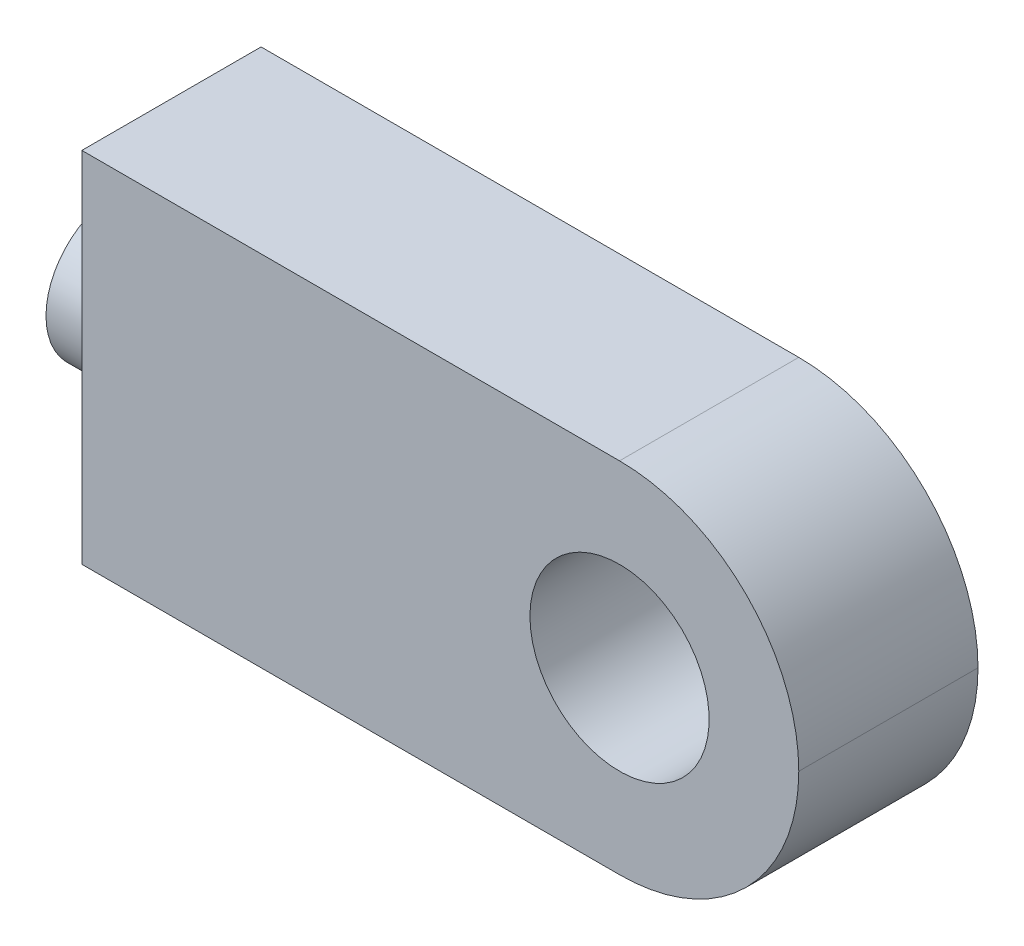
SolidWorks part; units mm, degrees
ref_plane "前视基准面" through (0, 0, 0) normal (0, 0, 1) x (1, 0, 0)
ref_plane "上视基准面" through (0, 0, 0) normal (0, 1, 0) x (1, 0, 0)
ref_plane "右视基准面" through (0, 0, 0) normal (1, 0, 0) x (0, 0, -1)
other "Configuration Table"
sketch "草图2" plane through (0, 0, 0) normal (0, 0, 1) x (1, 0, 0)
  line L1 (-40, -20) -> (40, -20)
  line L2 (-40, -20) -> (-40, 20)
  line L3 (-40, 20) -> (40, 20)
  line L4 (40, -20) -> (40, 20)
  line L5 (-40, -20) -> (40, 20) construction
  line L6 (-40, 20) -> (40, -20) construction
  point P0 (0, 0)
  dimension "D1" = 40
  dimension "D2" = 80
extrude "凸台-拉伸1" add sketch "草图2" along normal mid plane 20 contours L3 L4 L1 L2
fillet "圆角3" radius 20 2 edges at (40, -20, 0) (40, 20, 0)
sketch "草图8" plane through (0, 0, -10) normal (0, 0, -1) x (-1, 0, 0)
  circle A0 centre (-20, 0) radius 10
  dimension "D1" = 20
extrude "切除-拉伸6" cut sketch "草图8" against normal up to next
sketch "草图9" plane through (-40, 0, 0) normal (-1, 0, 0) x (0, 0, 1)
  circle A0 centre (0, 0) radius 8
  dimension "D1" = 16
extrude "凸台-拉伸2" add sketch "草图9" along normal blind 6
